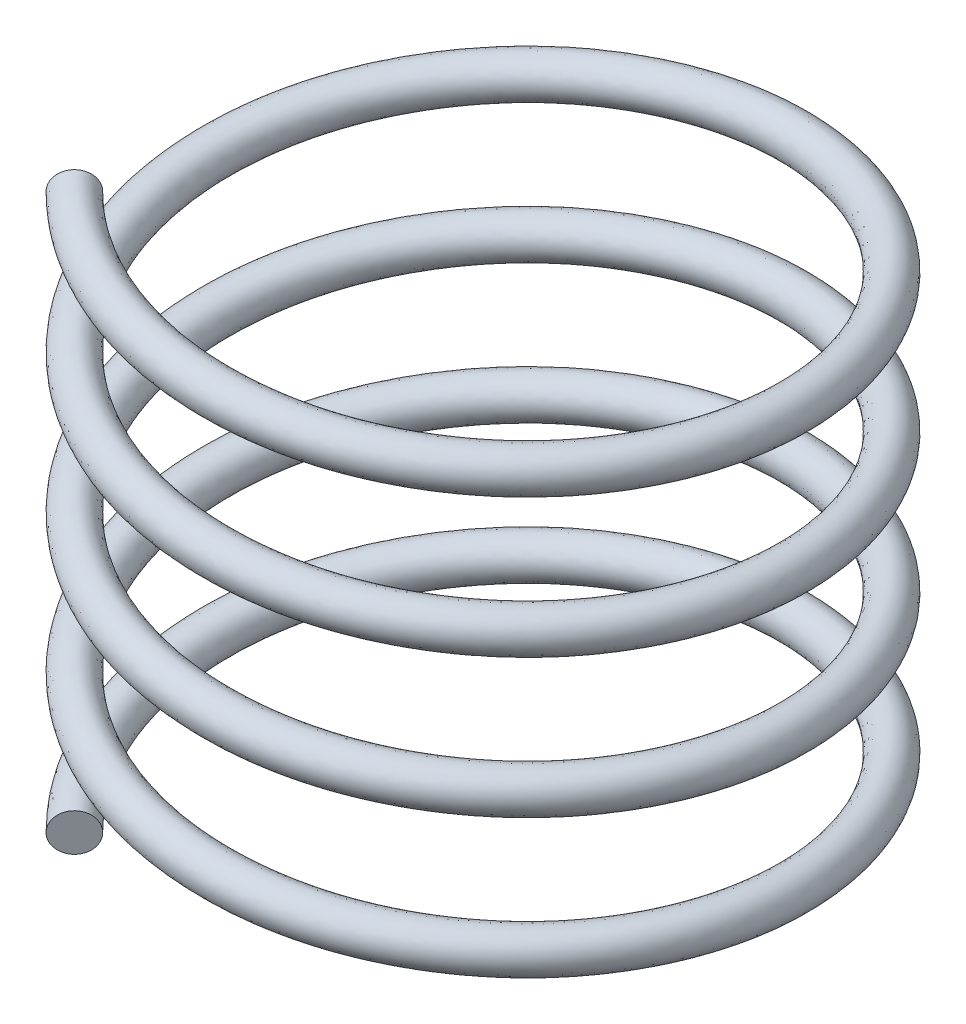
SolidWorks part; units mm, degrees
note: The reader was unsure of these and kept them because the rebuilt part matched: shared geometry of "Sketch1<2>".
ref_plane "Front Plane" through (0, 0, 0) normal (0, 0, 1) x (1, 0, 0)
ref_plane "Top Plane" through (0, 0, 0) normal (0, 1, 0) x (1, 0, 0)
ref_plane "Right Plane" through (0, 0, 0) normal (1, 0, 0) x (0, 0, -1)
sketch "Sketch1" plane through (0, 0, 0) normal (0, 1, 0) x (1, 0, 0)
  circle A0 centre (0, 0) radius 4.675
  dimension "D1" = 9.35
curve "Helix/Spiral1" pitch 2.25 height 9 turns 4 parameters "length"=9
ref_plane "Plane2" through (-3.3057, 0, 3.3057) normal (-0.705, 0.0764, -0.705) x (-0.698, 0.1008, 0.7089)
sketch "Sketch4" plane through (-3.3057, 0, 3.3057) normal (-0.705, 0.0764, -0.705) x (-0.698, 0.1008, 0.7089)
  circle A0 centre (0.0093, 0.0036) radius 0.325
  dimension "D1" = 0.65
sweep "Sweep1" add profiles "Sketch4" path "Helix/Spiral1"
surface "Surface-Extrude2" sketch "Sketch1<2>"
sketch "Sketch1<2>" plane through (0, 0, 0) normal (0, 1, 0) x (1, 0, 0) same geometry as "Sketch1"
